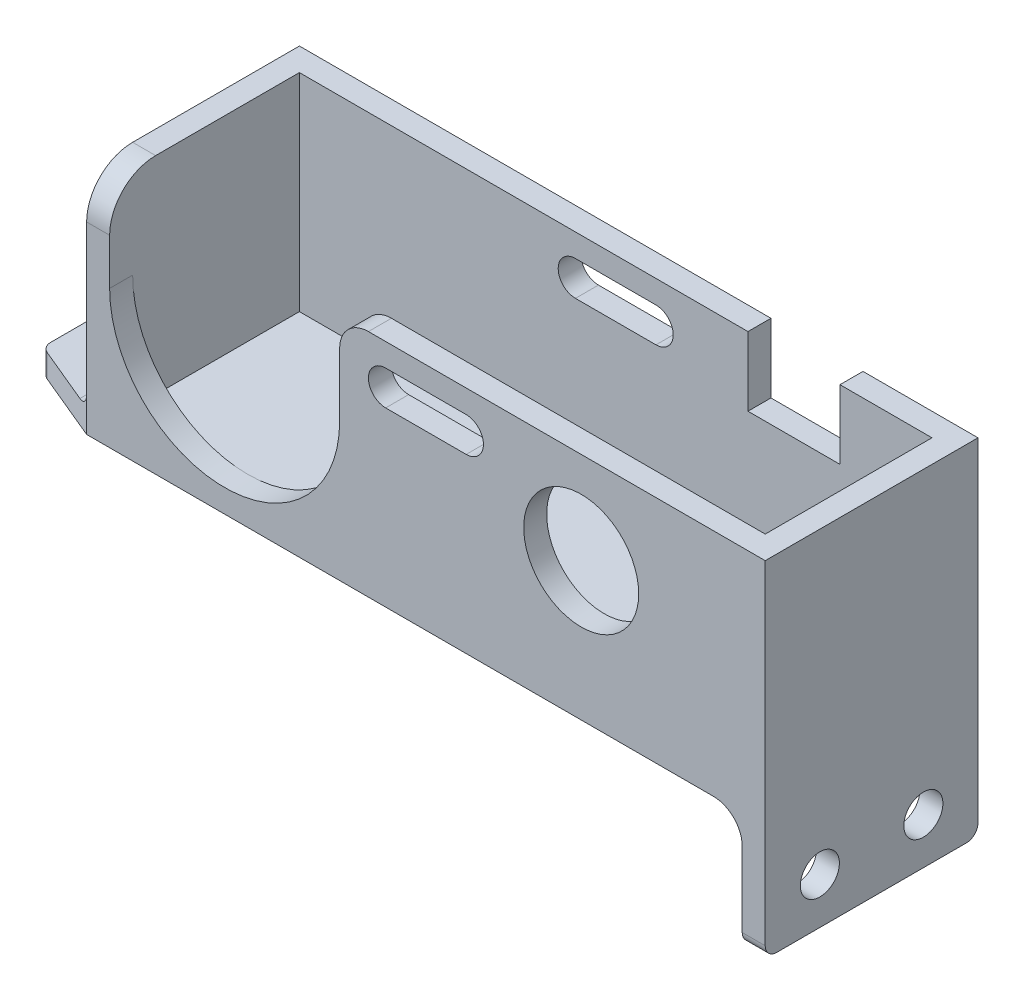
SolidWorks part; units mm, degrees
other "Markup1"
sketch "Sketch4" plane through (-28, -10, 6.5) normal (-0.9519, -0.1137, 0.2847) x (0.2678, 0.1434, 0.9527)
ref_plane "Front Plane" through (0, 0, 0) normal (0, 0, 1) x (1, 0, 0)
ref_plane "Top Plane" through (0, 0, 0) normal (0, 1, 0) x (1, 0, 0)
ref_plane "Right Plane" through (0, 0, 0) normal (1, 0, 0) x (0, 0, -1)
sketch "Sketch1" plane through (0, 0, 0) normal (0, 0, 1) x (1, 0, 0)
  line L0 (-27.5, 0) -> (27.5, 0) construction
  line L1 (-27.5, 9) -> (27.5, 9)
  line L2 (-27.5, -9) -> (27.5, -9)
  line L5 (-27.5, 9) -> (-27.5, -9)
  line L6 (0, 9) -> (0, -9) construction
  line L8 (27.5, 9) -> (27.5, -9)
  point P2 (0, 0)
  dimension "D1" = 55
  dimension "D2" = 18
extrude "Boss-Extrude1" add sketch "Sketch1" along normal mid plane 14.5
shell "Shell2" thickness 2 removed face at (0, 9, 0) outward yes
sketch "Sketch11" plane through (0, 0, 9.25) normal (0, 0, 1) x (1, 0, 0)
  line L0 (-27.5, 9) -> (-27.5, 1)
  line L1 (29.5, 9) -> (-29.5, 9) construction
  line L2 (-7.5, 1) -> (-7.5, 9)
  line L3 (-27.5, 9) -> (-7.5, 9)
  line L4 (-27.5, -9) -> (27.5, -9) construction
  arc A0 (-27.5, 1) -> (-7.5, 1) centre (-17.5, 1) ccw
  dimension "D1" = 10
extrude "lens cutout" cut sketch "Sketch11" against normal up to next
sketch "Sketch12" plane through (0, 0, 9.25) normal (0, 0, 1) x (1, 0, 0)
  line L2 (13.5, 1) -> (-17.5, 1) construction
  circle A0 centre (13.5, 1) radius 5
  arc A1 (-27.5, 1) -> (-7.5, 1) centre (-17.5, 1) ccw construction
  dimension "D2" = 10
  dimension "D1" = 31
extrude "power button hole" cut sketch "Sketch12" against normal up to next
sketch "Sketch13" plane through (0, 0, -9.25) normal (0, 0, -1) x (-1, 0, 0)
  line L2 (-29.5, 9) -> (29.5, 9) construction
  line L3 (-19.5, 9) -> (-11.5, 9)
  line L4 (-19.5, 9) -> (-19.5, 3)
  line L5 (-19.5, 3) -> (-11.5, 3)
  line L6 (-11.5, 9) -> (-11.5, 3)
  arc A0 (7.5, 1) -> (17.5, -9) centre (17.5, 1) ccw construction
  point P0 (17.5, 1)
  dimension "D1" = 29
  dimension "D2" = 2
  dimension "D3" = 8
extrude "power cord cutout" cut sketch "Sketch13" against normal up to next
sketch "Sketch21" plane through (0, 0, 9.25) normal (0, 0, 1) x (1, 0, 0)
  line L0 (-3.5, 5.5) -> (3.5, 5.5) construction
  line L1 (-3.5, 7) -> (3.5, 7)
  line L2 (-3.5, 4) -> (3.5, 4)
  line L3 (29.5, 9) -> (-7.5, 9) construction
  arc A0 (-3.5, 7) -> (-3.5, 4) centre (-3.5, 5.5) ccw
  arc A1 (3.5, 4) -> (3.5, 7) centre (3.5, 5.5) ccw
  point P2 (0, 5.5)
  point P7 (-5, 5.5)
  dimension "D1" = 3
  dimension "D2" = 10
  dimension "D3" = 2
extrude "Cut-Extrude4" cut sketch "Sketch21" against normal through all
fillet "Fillet4" radius 2.5 1 edges at (-7.5, 9, 8.25)
sketch "Sketch15" plane through (0, -11, 0) normal (0, -1, 0) x (1, 0, 0)
  line L0 (-29.5, 9.25) -> (-29.5, -9.25)
  line L1 (-29.5, -9.25) -> (-36, -11.9646)
  line L2 (-36, -11.9646) -> (-36, 6.5354)
  line L3 (-36, 6.5354) -> (-29.5, 9.25)
  dimension "D1" = 67.333
  dimension "D2" = 6.5
extrude "Boss-Extrude3" add sketch "Sketch15" against normal blind 2
hole_wizard "M3 Clearance Hole1" positions "Sketch16" profile "Sketch17" hole size "M3" standard "ANSI Metric" end condition through all
sketch "Sketch16" plane through (0, -9, 0) normal (0, 1, 0) x (1, 0, 0)
  line L0 (-32.75, 10.6073) -> (-32.75, -7.8927) construction
  line L1 (-36, 11.9646) -> (-29.5, 9.25) construction
  line L2 (-29.5, -9.25) -> (-36, -6.5354) construction
  line L6 (-32.75, 1.3573) -> (-36, 1.3573) construction
  line L7 (-36, -6.5354) -> (-36, 11.9646) construction
  point P16 (-32.75, 5.3573)
  point P18 (-32.75, -2.6427)
  dimension "D1" = 8
sketch "Sketch17" plane through (-32.75, -9, 2.6427) normal (1, 0, 0) x (0, 0, 1)
  line L0 (0, 0) -> (0, 2)
  line L1 (0, 2) -> (1.7, 2)
  line L2 (1.7, 2) -> (1.7, 0)
  line L5 (1.7, 0) -> (0, 0)
  line L11 (0, -6.35) -> (0, 107.95) construction
  dimension "Thru Hole Dia." = 3.4
  dimension "Thru Hole Depth" = 2
fillet "Fillet2" radius 1 1 edges at (-29.5, -9, 0)
sketch "Sketch18" plane through (0, -11, 0) normal (0, -1, 0) x (1, 0, 0)
  line L0 (-29.5, -9.25) -> (29.5, -9.25) construction
  line L1 (29.5, 9.25) -> (27.5, 9.25)
  line L2 (29.5, 9.25) -> (29.5, -9.25)
  line L3 (29.5, -9.25) -> (27.5, -9.25)
  line L4 (27.5, 9.25) -> (27.5, -9.25)
  dimension "D1" = 2
extrude "Boss-Extrude4" add sketch "Sketch18" along normal blind 10
hole_wizard "M3 Clearance Hole2" positions "Sketch19" profile "Sketch20" hole size "M3" standard "ANSI Metric" end condition through all
sketch "Sketch19" plane through (27.5, 0, 0) normal (-1, 0, 0) x (0, 0, 1)
  line L0 (0, -21) -> (0, -11) construction
  line L1 (9.25, -21) -> (-9.25, -21) construction
  line L2 (9.25, -11) -> (-9.25, -11) construction
  point P0 (-4.5, -17)
  point P2 (4.5, -17)
  dimension "D1" = 9
  dimension "D2" = 4
sketch "Sketch20" plane through (27.5, -17, -4.5) normal (0, 1, 0) x (0, 0, 1)
  line L0 (0, 0) -> (0, 2)
  line L1 (0, 2) -> (1.7, 2)
  line L2 (1.7, 2) -> (1.7, 0)
  line L5 (1.7, 0) -> (0, 0)
  line L11 (0, -6.35) -> (0, 107.95) construction
  dimension "Thru Hole Dia." = 3.4
  dimension "Thru Hole Depth" = 2
fillet "Fillet3" radius 2.5 1 edges at (27.5, -11, 0)
fillet "Fillet5" radius 4 1 edges at (-28.5, 9, 9.25)
fillet "Fillet6" radius 1 4 edges at (28.5, -21, -9.25) (28.5, -21, 9.25) (-36, -10, -11.9646) (-36, -10, 6.5354)
equation "\"wallthickness\"= 2"
equation "\"D1@Shell2\"=\"wallthickness\""
equation "\"D1@Boss-Extrude3\"=\"wallthickness\""
equation "\"D1@Sketch18\"=\"wallthickness\""
